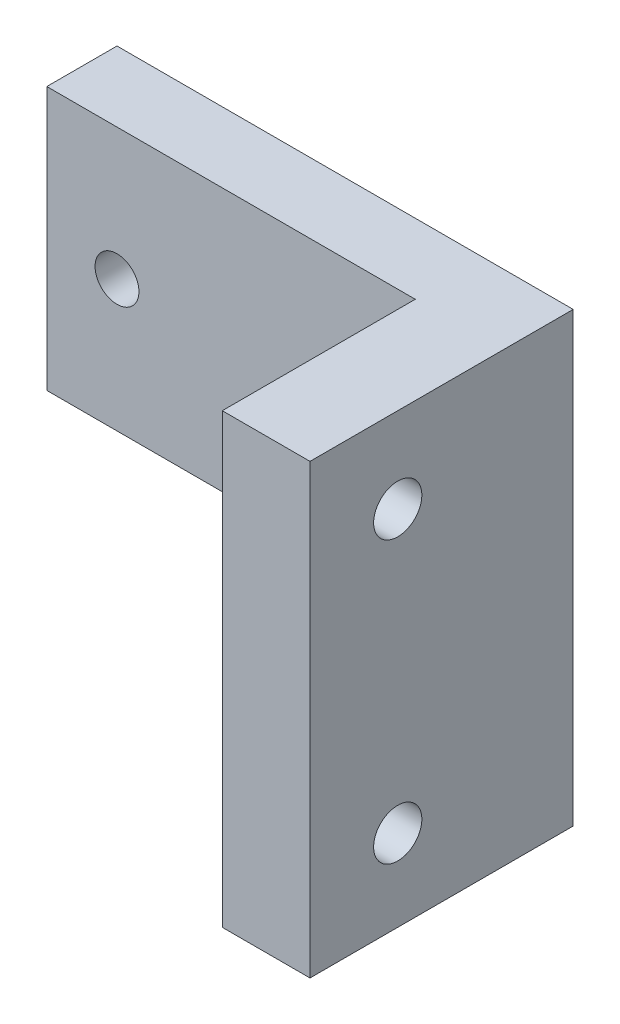
SolidWorks part; units mm, degrees
ref_plane "Plan de face" through (0, 0, 0) normal (0, 0, 1) x (1, 0, 0)
ref_plane "Plan de dessus" through (0, 0, 0) normal (0, 1, 0) x (1, 0, 0)
ref_plane "Plan de droite" through (0, 0, 0) normal (1, 0, 0) x (0, 0, -1)
sketch "Sketch1" plane through (0, 0, 0) normal (0, 0, 1) x (1, 0, 0)
  line L1 (0, 0) -> (42, 0)
  line L2 (0, 0) -> (0, 30)
  line L3 (0, 30) -> (42, 30)
  line L4 (42, 0) -> (42, 30)
  line L5 (42, 0) -> (52, 0)
  line L6 (42, 0) -> (42, 148)
  line L7 (42, 148) -> (52, 148)
  line L8 (52, 0) -> (52, 148)
  line L9 (42, 148) -> (0, 148)
  line L10 (42, 148) -> (42, 118)
  line L11 (42, 118) -> (0, 118)
  line L12 (0, 148) -> (0, 118)
  dimension "D1" = 42
  dimension "D2" = 30
  dimension "D3" = 42
  dimension "D4" = 30
  dimension "D5" = 148
  dimension "D6" = 10
extrude "Boss-Extrude1" add sketch "Sketch1" along normal blind 8 contours L9 L12 L11 L6 | L1 L4 L3 L2 region at (21, 15, 0) region at (21, 133, 0)
extrude "Boss-Extrude2" add sketch "Sketch1<3>" along normal blind 30 contours L5 L8 L7 L6 L4 region at (47, 74, 0)
sketch "Sketch1<3>" plane through (0, 0, 0) normal (0, 0, 1) x (1, 0, 0) same geometry as "Sketch1"
sketch "Sketch2" plane through (0, 0, 8) normal (0, 0, 1) x (1, 0, 0)
  line L0 (42, 148) -> (0, 148) construction
  line L1 (0, 148) -> (0, 118) construction
  line L2 (42, 0) -> (42, 148) construction
  line L3 (52, 74) -> (0, 74) construction
  line L4 (52, 0) -> (52, 148) construction
  circle A0 centre (8, 133) radius 2.5
  circle A1 centre (34, 133) radius 2.5
  circle A2 centre (34, 15) radius 2.5
  circle A3 centre (8, 15) radius 2.5
  dimension "D1" = 5
  dimension "D2" = 5
  dimension "D3" = 15
  dimension "D4" = 8
  dimension "D5" = 8
extrude "Cut-Extrude1" cut sketch "Sketch2" against normal up to surface (8 mm away) up to face at (26.125, 68.5, 0)
sketch "Sketch3" plane through (52, 0, 0) normal (1, 0, 0) x (0, 0, -1)
  line L1 (-30, 148) -> (0, 148) construction
  line L2 (-30, 0) -> (-30, 148) construction
  circle A0 centre (-20, 138.3) radius 2.75
  circle A1 centre (-20, 106.3) radius 2.75
  circle A2 centre (-20, 41.2) radius 2.75
  circle A3 centre (-20, 9.2) radius 2.75
  dimension "D2" = 5.5
  dimension "D3" = 5.5
  dimension "D10" = 5.5
  dimension "D11" = 5.5
  dimension "D1" = 32
  dimension "D4" = 9.7
  dimension "D5" = 10
  dimension "D6" = 65.1
  dimension "D7" = 32
  dimension "D8" = 10
  dimension "D9" = 10
extrude "Cut-Extrude2" cut sketch "Sketch3" against normal up to surface (10 mm away) up to face at (42, 66.625, 13.375)
sketch "Sketch6" plane through (0, 0, 0) normal (-1, 0, 0) x (0, 0, 1)
  line L0 (30, 0) -> (30, 148) construction
  line L1 (0, 0) -> (30, 0)
  line L2 (0, 0) -> (0, 97)
  line L3 (0, 97) -> (30, 97)
  line L4 (30, 0) -> (30, 97)
  dimension "D1" = 97
extrude "Cut-Extrude6" cut sketch "Sketch6" against normal up to surface (52 mm away) up to face at (52, 9.2, 22.75)
